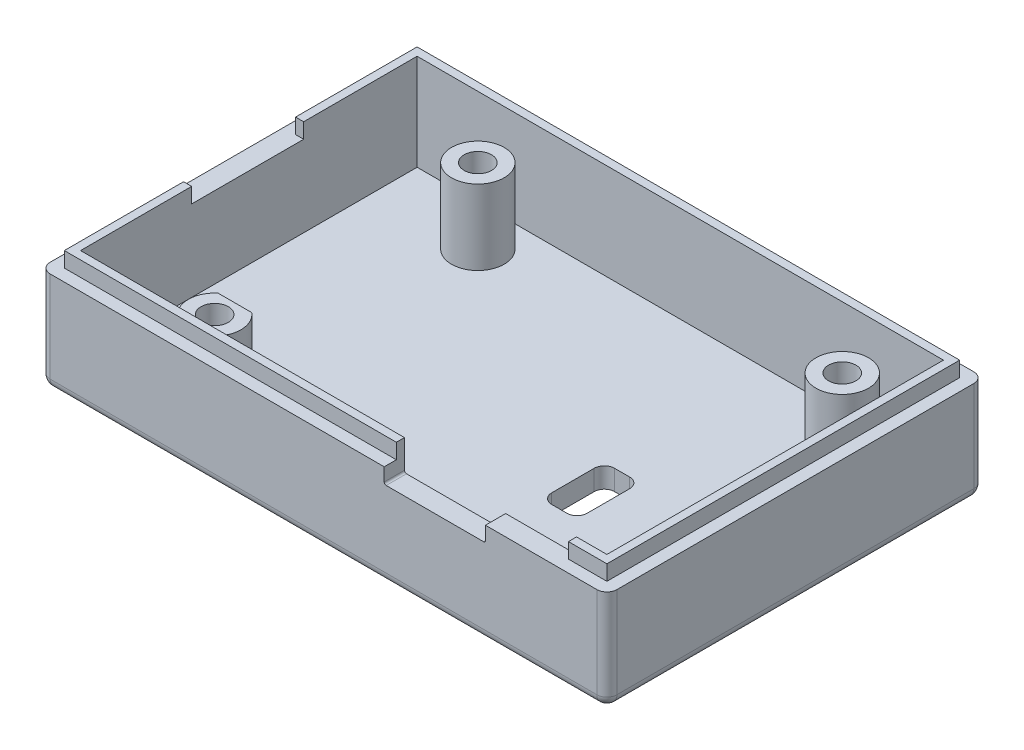
SolidWorks part; units mm, degrees
ref_plane "Front Plane" through (0, 0, 0) normal (0, 0, 1) x (1, 0, 0)
ref_plane "Top Plane" through (0, 0, 0) normal (0, 1, 0) x (1, 0, 0)
ref_plane "Right Plane" through (0, 0, 0) normal (1, 0, 0) x (0, 0, -1)
sketch "Sketch1" plane through (0, 0, 0) normal (0, 1, 0) x (1, 0, 0)
  line L0 (0, 0) -> (56, 0)
  line L1 (56, 0) -> (56, 37.25)
  line L2 (56, 37.25) -> (0, 37.25)
  line L3 (0, 37.25) -> (0, 0)
  dimension "D1" = 56
  dimension "D2" = 37.25
extrude "Boss-Extrude1" add sketch "Sketch1" along normal blind 2
sketch "Sketch2" plane through (0, 2, 0) normal (0, 1, 0) x (1, 0, 0)
  line L0 (2, 35.25) -> (2, 2)
  line L1 (2, 2) -> (54, 2)
  line L2 (0, 37.25) -> (0, 0) construction
  line L3 (0, 0) -> (56, 0) construction
  line L4 (2, 35.25) -> (54, 35.25)
  line L5 (54, 35.25) -> (54, 2)
  line L6 (56, 0) -> (56, 37.25) construction
  line L7 (56, 37.25) -> (0, 37.25) construction
  line L12 (0, 37.25) -> (0, 0)
  line L13 (0, 0) -> (56, 0)
  line L14 (56, 0) -> (56, 37.25)
  line L15 (56, 37.25) -> (0, 37.25)
  line L16 (0, 37.25) -> (0, 0)
  line L17 (0, 0) -> (56, 0)
  line L18 (56, 0) -> (56, 37.25)
  line L19 (56, 37.25) -> (0, 37.25)
  dimension "D1" = 2
  dimension "D2" = 2
  dimension "D3" = 2
  dimension "D4" = 2
  dimension "D5" = 0
extrude "Boss-Extrude2" add sketch "Sketch2" along normal blind 9
sketch "Sketch3" plane through (0, 2, 0) normal (0, 1, 0) x (1, 0, 0)
  line L0 (54, 2) -> (54, 35.25) construction
  line L1 (54, 35.25) -> (2, 35.25) construction
  line L2 (12, 5.25) -> (12, 31.25) construction
  line L3 (12, 31.25) -> (48, 31.25) construction
  circle A0 centre (12, 5.25) radius 2.6
  circle A1 centre (12, 31.25) radius 2.6
  circle A2 centre (48, 31.25) radius 2.6
  circle A3 centre (12, 5.25) radius 1.35
  circle A4 centre (12, 31.25) radius 1.35
  circle A5 centre (48, 31.25) radius 1.35
  dimension "D1" = 26
  dimension "D2" = 6
  dimension "D3" = 36
  dimension "D4" = 4
extrude "Boss-Extrude3" add sketch "Sketch3" along normal blind 7.4
sketch "Sketch4" plane through (0, 2, 0) normal (0, 1, 0) x (1, 0, 0)
  circle A0 centre (12, 5.25) radius 1.35 construction
  circle A1 centre (48, 31.25) radius 1.35 construction
  circle A2 centre (12, 31.25) radius 1.35 construction
  circle A3 centre (12, 5.25) radius 1.35
  circle A4 centre (48, 31.25) radius 1.35
  circle A5 centre (12, 31.25) radius 1.35
extrude "Boss-Extrude4" [suppressed] add sketch "Sketch4" along normal blind 3.4
sketch "Sketch5" plane through (0, 11, 0) normal (0, 1, 0) x (1, 0, 0)
  line L0 (1.2, 1.2) -> (54.8, 1.2)
  line L1 (0, 0) -> (56, 0) construction
  line L2 (54.8, 1.2) -> (54.8, 36.05)
  line L3 (54.8, 36.05) -> (1.2, 36.05)
  line L4 (1.2, 36.05) -> (1.2, 1.2)
  line L5 (56, 0) -> (56, 37.25) construction
  line L6 (56, 37.25) -> (0, 37.25) construction
  line L7 (0, 37.25) -> (0, 0) construction
  line L8 (0, 37.25) -> (0, 0)
  line L9 (56, 37.25) -> (0, 37.25)
  line L10 (56, 0) -> (56, 37.25)
  line L11 (0, 0) -> (56, 0)
  dimension "D1" = 1.2
  dimension "D2" = 1.2
  dimension "D3" = 1.2
  dimension "D4" = 1.2
extrude "Cut-Extrude1" cut sketch "Sketch5" against normal blind 1
sketch "Sketch6" [suppressed] plane through (0, 5.4, 0) normal (0, 1, 0) x (1, 0, 0)
  circle A0 centre (12, 5.25) radius 1
  circle A1 centre (12, 31.25) radius 1
  circle A2 centre (48, 31.25) radius 1
  circle A3 centre (48, 31.25) radius 1.5 construction
  circle A4 centre (12, 31.25) radius 1.5 construction
  circle A5 centre (12, 5.25) radius 1.5 construction
  circle A6 centre (48, 31.25) radius 1.5
  circle A7 centre (12, 31.25) radius 1.5
  circle A8 centre (12, 5.25) radius 1.5
extrude "Boss-Extrude5" [suppressed] add sketch "Sketch6" along normal blind 5
fillet "Fillet1" radius 1 4 edges at (56, 5, -37.25) (56, 5, 0) (0, 5, -37.25) (0, 5, 0)
sketch "Sketch7" plane through (0, 2, 0) normal (0, 1, 0) x (1, 0, 0)
  circle A0 centre (12, 5.25) radius 1.35 construction
  circle A1 centre (48, 31.25) radius 1.35 construction
  circle A2 centre (12, 31.25) radius 1.35 construction
  circle A3 centre (12, 5.25) radius 1.35
  circle A4 centre (48, 31.25) radius 1.35
  circle A5 centre (12, 31.25) radius 1.35
extrude "Cut-Extrude2" cut sketch "Sketch7" against normal blind 10
sketch "Sketch8" plane through (0, 0, 0) normal (0, 0, 1) x (1, 0, 0)
  line L0 (44, 10) -> (44, 8.5)
  line L1 (1, 10) -> (55, 10) construction
  line L2 (34, 10) -> (34, 8.5)
  line L3 (34, 8.5) -> (44, 8.5)
  line L4 (34, 12.3) -> (34, 10) construction
  line L6 (34, 10) -> (44, 10) construction
  line L7 (34, 10) -> (34, 11)
  line L8 (34, 11) -> (44, 11)
  line L9 (44, 11) -> (44, 10)
  line L10 (1.2, 11) -> (54.8, 11) construction
  dimension "D1" = 2.5
extrude "Cut-Extrude3" cut sketch "Sketch8" against normal blind 3
fillet "Fillet2" radius 1 8 edges at (55.7071, 0, -0.2929) (28, 0, 0) (0.2929, 0, -0.2929) (0, 0, -18.625) (0.2929, 0, -36.9571) (28, 0, -37.25) (55.7071, 0, -36.9571) (56, 0, -18.625)
sketch "Sketch9" plane through (0, 9.4, 0) normal (0, 1, 0) x (1, 0, 0)
  line L0 (12, 5.25) -> (12, 7.25) construction
  line L1 (12, 7.25) -> (13.6613, 7.25)
  line L2 (12, 7.25) -> (10.3387, 7.25)
  circle A0 centre (12, 5.25) radius 2.6 construction
  arc A1 (13.6613, 7.25) -> (10.3387, 7.25) centre (12, 5.25) ccw
extrude "Cut-Extrude4" cut sketch "Sketch9" against normal up to surface (7.4 mm away) up to face at (48, 2, -28.65)
sketch "Sketch10" plane through (0, 2, 0) normal (0, 1, 0) x (1, 0, 0)
  line L0 (54, 2) -> (54, 35.25) construction
  line L1 (36.5, 19.25) -> (40, 19.25)
  line L2 (36.5, 19.25) -> (36.5, 13.05)
  line L3 (36.5, 13.05) -> (40, 13.05)
  line L4 (40, 19.25) -> (40, 13.05)
  line L5 (54, 35.25) -> (2, 35.25) construction
  point P4 (38.25, 13.05)
  dimension "D1" = 3.5
  dimension "D2" = 6.2
  dimension "D3" = 14
  dimension "D4" = 16
extrude "Cut-Extrude5" cut sketch "Sketch10" against normal blind 10
fillet "Fillet3" radius 1 4 edges at (40, 1, -13.05) (36.5, 1, -13.05) (40, 1, -19.25) (36.5, 1, -19.25)
sketch "Sketch11" plane through (0, 0, -1.2) normal (0, 0, 1) x (1, 0, 0)
  line L0 (51, 11) -> (51, 10)
  line L4 (44, 11) -> (44, 10)
  line L5 (44, 10) -> (54.8, 10)
  line L6 (54.8, 10) -> (54.8, 11)
  line L7 (54.8, 11) -> (44, 11)
  line L8 (44, 11) -> (44, 10)
  line L9 (44, 10) -> (51, 10)
  line L11 (51, 11) -> (44, 11)
  point P6 (44, 10.5)
  point P7 (51, 10.5)
  dimension "D2" = 7
  dimension "D1" = 0
extrude "Cut-Extrude6" cut sketch "Sketch11" against normal blind 10
fillet "Fillet4" radius 0.2 2 edges at (44, 8.5, -1) (34, 8.5, -1)
sketch "Sketch12" plane through (0, 11, 0) normal (0, 1, 0) x (1, 0, 0)
  line L12 (51, 2) -> (51, 1.2)
  line L13 (51, 1.2) -> (54.8, 1.2)
  line L14 (54.8, 1.2) -> (54.8, 36.05)
  line L15 (54.8, 36.05) -> (1.2, 36.05)
  line L16 (1.2, 36.05) -> (1.2, 1.2)
  line L17 (1.2, 1.2) -> (34, 1.2)
  line L18 (34, 1.2) -> (34, 2)
  line L19 (34, 2) -> (2, 2)
  line L20 (2, 2) -> (2, 35.25)
  line L21 (2, 35.25) -> (54, 35.25)
  line L22 (54, 35.25) -> (54, 2)
  line L23 (54, 2) -> (51, 2)
  line L24 (51, 2) -> (51, 1.2)
  line L25 (51, 1.2) -> (54.8, 1.2)
  line L26 (54.8, 1.2) -> (54.8, 36.05)
  line L27 (54.8, 36.05) -> (1.2, 36.05)
  line L28 (1.2, 36.05) -> (1.2, 1.2)
  line L29 (1.2, 1.2) -> (34, 1.2)
  line L30 (34, 1.2) -> (34, 2)
  line L31 (34, 2) -> (2, 2)
  line L32 (2, 2) -> (2, 35.25)
  line L33 (2, 35.25) -> (54, 35.25)
  line L34 (54, 35.25) -> (54, 2)
  line L35 (54, 2) -> (51, 2)
  dimension "D1" = 0
extrude "Boss-Extrude6" add sketch "Sketch12" along normal blind 0.5
sketch "Sketch13" plane through (1.2, 0, 0) normal (-1, 0, 0) x (0, 0, 1)
  line L0 (-12.98, 11.5) -> (-12.98, 10)
  line L1 (-36.05, 11.5) -> (-1.2, 11.5) construction
  line L2 (-36.05, 10) -> (-1.2, 10) construction
  line L3 (0, 10) -> (0, 1) construction
  line L4 (-12.98, 11.5) -> (-24.0434, 11.5)
  line L5 (-24.0434, 11.5) -> (-24.0434, 10)
  line L6 (-24.0434, 10) -> (-12.98, 10)
  dimension "D1" = 12.98
  dimension "D2" = 11.0634
extrude "Cut-Extrude9" cut sketch "Sketch13" against normal blind 2
